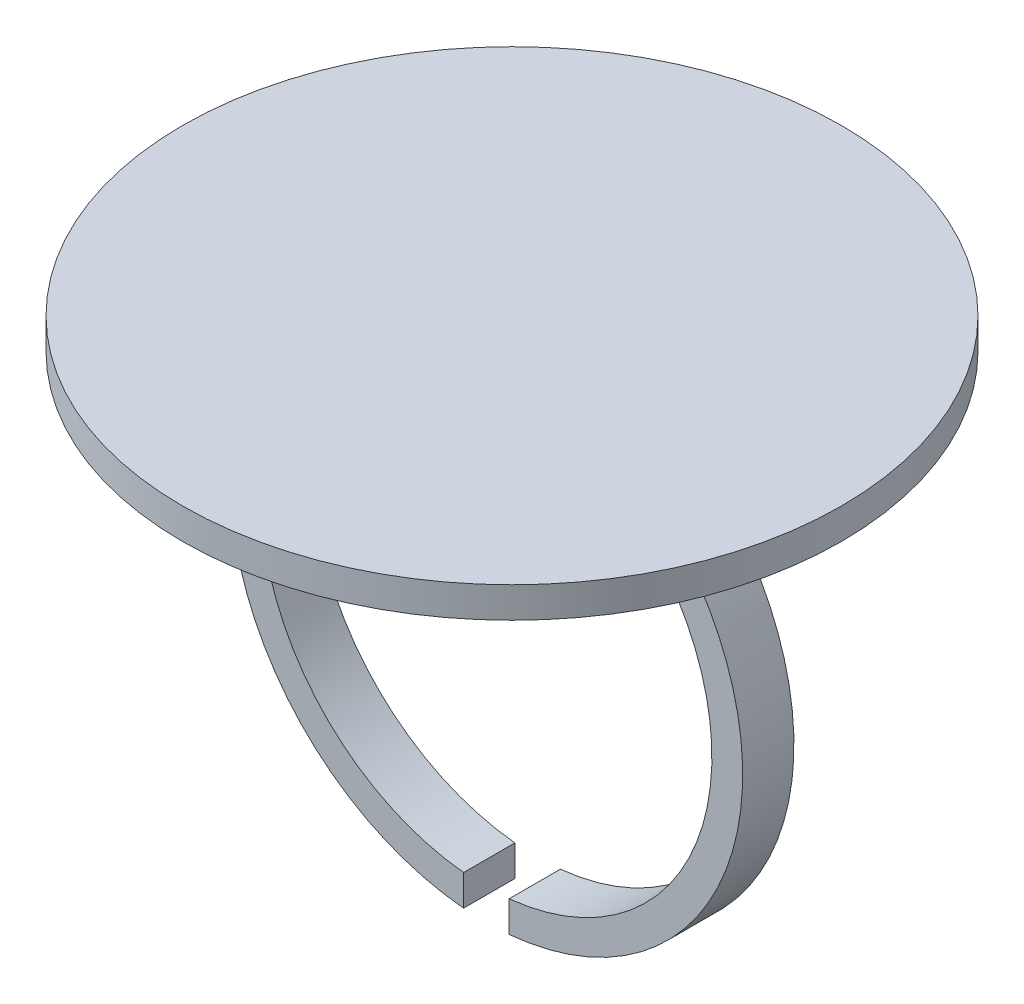
SolidWorks part; units mm, degrees
ref_plane "Plan de face" through (0, 0, 0) normal (0, 0, 1) x (1, 0, 0)
ref_plane "Plan de dessus" through (0, 0, 0) normal (0, 1, 0) x (1, 0, 0)
ref_plane "Plan de droite" through (0, 0, 0) normal (1, 0, 0) x (0, 0, -1)
sketch "Esquisse1" plane through (0, 0, 0) normal (0, 1, 0) x (1, 0, 0)
  circle A0 centre (0, 0) radius 32.1391
  point P3 (0, 0)
extrude "Boss.-Extru.1" add sketch "Esquisse1" along normal blind 3
sketch "Esquisse2" plane through (0, 0, 0) normal (0, 0, 1) x (1, 0, 0)
  circle A0 centre (0, -22) radius 25
extrude "Boss.-Extru.2" add sketch "Esquisse2" along normal blind 2.5 and the other way blind 2.5
sketch "Esquisse3" plane through (0, 0, 2.5) normal (0, 0, 1) x (1, 0, 0)
  circle A0 centre (0, -22) radius 22
extrude "Enlèv. mat.-Extru.1" cut sketch "Esquisse3" against normal blind 5
sketch "Esquisse7" plane through (0, 0, 2.5) normal (0, 0, 1) x (1, 0, 0)
  line L1 (-2.2192, -41.7243) -> (2.2192, -41.7243)
  line L2 (-2.2192, -41.7243) -> (-2.2192, -50)
  line L3 (-2.2192, -50) -> (2.2192, -50)
  line L4 (2.2192, -41.7243) -> (2.2192, -50)
  line L5 (-2.2192, -41.7243) -> (2.2192, -50) construction
  line L6 (-2.2192, -50) -> (2.2192, -41.7243) construction
  point P0 (0, -45.8622)
extrude "Enlèv. mat.-Extru.4" cut sketch "Esquisse7" against normal blind 5
sketch "Esquisse6" plane through (0, 0, -2.5) normal (0, 0, -1) x (-1, 0, 0)
